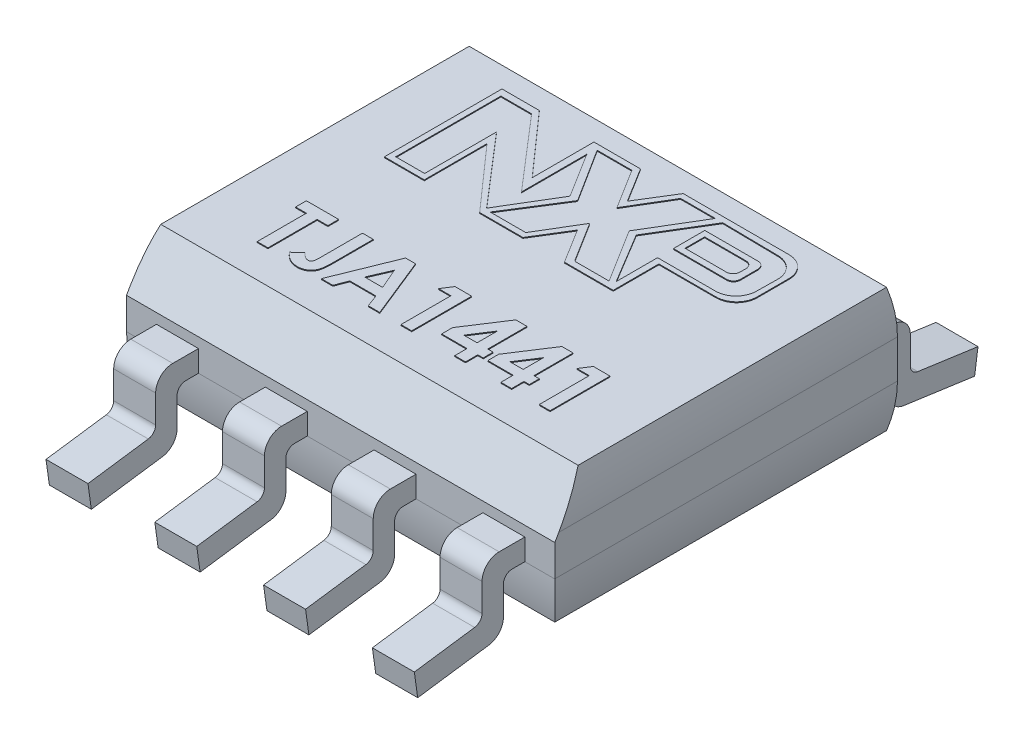
SolidWorks part; units mm, degrees
ref_plane "Front Plane" through (0, 0, 0) normal (0, 0, 1) x (1, 0, 0)
ref_plane "Top Plane" through (0, 0, 0) normal (0, 1, 0) x (1, 0, 0)
ref_plane "Right Plane" through (0, 0, 0) normal (1, 0, 0) x (0, 0, -1)
sketch "Sketch1" plane through (0, 0, 0) normal (0, 1, 0) x (1, 0, 0)
  line L1 (-2.5, 2) -> (2.5, 2)
  line L2 (-2.5, 2) -> (-2.5, -2)
  line L3 (-2.5, -2) -> (2.5, -2)
  line L4 (2.5, 2) -> (2.5, -2)
  line L5 (-2.5, 2) -> (2.5, -2) construction
  line L6 (-2.5, -2) -> (2.5, 2) construction
  point P0 (0, 0)
  dimension "D1" = 5
  dimension "D2" = 4
extrude "Boss-Extrude1" add sketch "Sketch1" along normal blind 1.45
sketch "Sketch2" plane through (-2.5, 0, 0) normal (-1, 0, 0) x (0, 0, 1)
  line L0 (2, 0.8687) -> (1.6644, 1.45)
  line L1 (2, 1.45) -> (2, 0) construction
  line L2 (-2, 1.45) -> (2, 1.45) construction
  line L3 (0, 0) -> (0, 0.828) construction
  line L4 (-2, 0.725) -> (-1.3983, 0.725) construction
  line L6 (-2, 1.45) -> (-2, 0) construction
  line L7 (-1.8644, 1.6723) -> (-2.1559, 1.6723)
  line L8 (-2.1559, 1.6723) -> (-2.1559, 0.954)
  line L9 (-2.1559, 0.954) -> (-2, 0.9484)
  line L10 (-2, 0.5016) -> (-2.1559, 0.5016)
  line L11 (-2.1559, 0.5016) -> (-2.1559, -0.2223)
  line L12 (-2.1559, -0.2223) -> (-1.8644, -0.2223)
  line L13 (1.6644, 1.45) -> (1.6644, 1.7317)
  line L14 (1.6644, 1.7317) -> (2.4871, 1.7317)
  line L15 (2.4871, 1.7317) -> (2.4871, 0.8687)
  line L16 (2.4871, 0.8687) -> (2, 0.8687)
  line L17 (2, 0.5015) -> (2.4871, 0.5015)
  line L18 (2.4871, 0.5015) -> (2.4871, -0.2223)
  line L19 (2.4871, -0.2223) -> (1.8644, -0.2223)
  arc A0 (2, 0.5015) -> (1.8644, -0.2223) centre (0, 0.5015) cw
  arc A1 (-2, 0.5016) -> (-1.8644, -0.2223) centre (0, 0.5015) ccw
  arc A2 (-2, 0.9484) -> (-1.8644, 1.6723) centre (0, 0.9485) cw
  dimension "D1" = 2
  dimension "D2" = 60
extrude "Cut-Extrude1" cut sketch "Sketch2" against normal blind 61.45
sketch "Sketch5" plane through (0, 0, -2) normal (0, 0, -1) x (-1, 0, 0)
  line L1 (0, 1.45) -> (0, 1.0867) construction
  line L2 (-3.4587, 0.725) -> (-2.857, 0.725) construction
  line L3 (-2.3644, 1.6723) -> (-2.6559, 1.6723)
  line L4 (-2.6559, 1.6723) -> (-2.6559, 0.954)
  line L5 (-2.6559, 0.954) -> (-2.5, 0.9484)
  line L6 (-2.5, 0.5016) -> (-2.6559, 0.5016)
  line L7 (-2.6559, 0.5016) -> (-2.6559, -0.2223)
  line L8 (-2.6559, -0.2223) -> (-2.3644, -0.2223)
  line L16 (2.5, 1.45) -> (-2.5, 1.45) construction
  line L17 (-2.6559, 1.6723) -> (-2.3644, 1.6723)
  line L18 (-2.6559, 0.9484) -> (-2.6559, 1.6723)
  line L19 (-2.5, 0.9484) -> (-2.6559, 0.9484)
  line L20 (-2.6559, 0.496) -> (-2.5, 0.5016)
  line L21 (-2.6559, -0.2223) -> (-2.6559, 0.496)
  line L22 (-2.3644, -0.2223) -> (-2.6559, -0.2223)
  line L23 (2.6559, -0.2223) -> (2.3644, -0.2223)
  line L24 (2.6559, 0.5016) -> (2.6559, -0.2223)
  line L25 (2.5, 0.5016) -> (2.6559, 0.5016)
  line L26 (2.6559, 0.954) -> (2.5, 0.9484)
  line L27 (2.6559, 1.6723) -> (2.6559, 0.954)
  line L28 (2.3644, 1.6723) -> (2.6559, 1.6723)
  arc A1 (-2.5, 0.5016) -> (-2.3644, -0.2223) centre (-0.5, 0.5015) ccw
  arc A2 (-2.5, 0.9484) -> (-2.3644, 1.6723) centre (-0.5, 0.9485) cw
  arc A3 (-2.5, 0.5016) -> (-2.3644, -0.2223) centre (-0.5, 0.5015) ccw
  arc A4 (-2.5, 0.9484) -> (-2.3644, 1.6723) centre (-0.5, 0.9485) cw
  arc A5 (2.5, 0.5016) -> (2.3644, -0.2223) centre (0.5, 0.5015) cw
  arc A6 (2.5, 0.9484) -> (2.3644, 1.6723) centre (0.5, 0.9485) ccw
extrude "Cut-Extrude2" cut sketch "Sketch5" against normal blind 61.45 contours L5 A2 L3 L4 | A1 L20 L7 L22 | A6 L26 L27 L28 | L25 A5 L23 L24
sketch "Sketch6" plane through (-2.5, 0, 0) normal (-1, 0, 0) x (0, 0, 1)
  line L5 (1.9361, 0) -> (-1.9361, 0) construction
  line L7 (0, 0) -> (0, -0.7239) construction
  line L8 (2.2535, 0.75) -> (2.3, 0.75)
  line L9 (2.5, 0.55) -> (2.5, 0.2276)
  line L10 (2.5, 0.1406) -> (3.25, 0.1406) construction
  line L11 (3.25, 0.1406) -> (3.25, -0.1094) construction
  line L12 (3.25, -0.1094) -> (2.25, -0.1094) construction
  line L13 (2.25, 0.0645) -> (2.25, 0.4)
  line L14 (2.25, 0.5) -> (2.2535, 0.5)
  line L15 (-3.25, -0.1094) -> (-2.25, -0.1094) construction
  line L17 (2.4222, -0.1335) -> (3.2508, -0.25)
  line L18 (2.5861, 0.1286) -> (3.2901, 0.0296)
  line L19 (3.2508, -0.25) -> (3.2901, 0.0296)
  line L20 (-3.25, 0.1406) -> (-3.25, -0.1094) construction
  line L21 (-2.5, 0.1406) -> (-3.25, 0.1406) construction
  line L22 (-3.2508, -0.25) -> (-3.2901, 0.0296)
  line L23 (-2.5861, 0.1286) -> (-3.2901, 0.0296)
  line L24 (-2.4222, -0.1335) -> (-3.2508, -0.25)
  line L25 (-2.25, 0.5) -> (-2.2535, 0.5)
  line L26 (-2.25, 0.0645) -> (-2.25, 0.4)
  line L27 (-2.5, 0.55) -> (-2.5, 0.2276)
  line L28 (-2.2535, 0.75) -> (-2.3, 0.75)
  line L29 (-2.15, 0.5) -> (2.15, 0.5)
  line L30 (-2.2535, 0.75) -> (2.2535, 0.75)
  arc A0 (2.4222, -0.1335) -> (2.25, 0.0645) centre (2.45, 0.0645) cw
  arc A1 (2.5, 0.55) -> (2.3, 0.75) centre (2.3, 0.55) ccw
  arc A2 (2.5861, 0.1286) -> (2.5, 0.2276) centre (2.6, 0.2276) cw
  arc A3 (2.25, 0.4) -> (2.15, 0.5) centre (2.15, 0.4) ccw
  arc A4 (-2.25, 0.4) -> (-2.15, 0.5) centre (-2.15, 0.4) cw
  arc A5 (-2.5861, 0.1286) -> (-2.5, 0.2276) centre (-2.6, 0.2276) ccw
  arc A6 (-2.5, 0.55) -> (-2.3, 0.75) centre (-2.3, 0.55) cw
  arc A7 (-2.4222, -0.1335) -> (-2.25, 0.0645) centre (-2.45, 0.0645) ccw
  dimension "D9" = 0.2
  dimension "D10" = 0.1
  dimension "D4" = 0.25
  dimension "D5" = 0.25
  dimension "D6" = 1
  dimension "D7" = 8
  dimension "D8" = 0.25
extrude "Boss-Extrude2" add sketch "Sketch6" against normal up to surface (5 mm away) up to face at (2.5, 0.8431, 0.3908)
sketch "Sketch7" plane through (0, 1.45, 0) normal (0, 1, 0) x (1, 0, 0)
  line L0 (2.5, -2) -> (-2.5, -2) construction
  line L1 (-2.5, -2) -> (-2.15, -2)
  line L2 (-2.5, -2) -> (-2.5, -3.534)
  line L3 (-2.5, -3.534) -> (-2.15, -3.534)
  line L4 (-2.15, -2) -> (-2.15, -3.534)
  line L5 (-1.66, -2) -> (-0.88, -2)
  line L6 (-1.66, -2) -> (-1.66, -3.6106)
  line L7 (-1.66, -3.6106) -> (-0.88, -3.6106)
  line L8 (-0.88, -2) -> (-0.88, -3.6106)
  line L9 (0, 0) -> (-3.4858, 0) construction
  line L10 (-0.39, -2) -> (0.39, -2)
  line L11 (-0.39, -2) -> (-0.39, -3.6106)
  line L12 (-0.39, -3.6106) -> (0.39, -3.6106)
  line L13 (0.39, -2) -> (0.39, -3.6106)
  line L14 (2.5, -2) -> (2.15, -2)
  line L15 (2.5, -2) -> (2.5, -3.783)
  line L16 (2.5, -3.783) -> (2.15, -3.783)
  line L17 (2.15, -2) -> (2.15, -3.783)
  line L18 (1.66, -2) -> (0.88, -2)
  line L19 (1.66, -2) -> (1.66, -3.6776)
  line L20 (1.66, -3.6776) -> (0.88, -3.6776)
  line L21 (0.88, -2) -> (0.88, -3.6776)
  line L22 (0.88, 2) -> (0.88, 3.6776)
  line L23 (1.66, 3.6776) -> (0.88, 3.6776)
  line L24 (1.66, 2) -> (1.66, 3.6776)
  line L25 (1.66, 2) -> (0.88, 2)
  line L26 (2.15, 2) -> (2.15, 3.783)
  line L27 (2.5, 3.783) -> (2.15, 3.783)
  line L28 (2.5, 2) -> (2.5, 3.783)
  line L29 (2.5, 2) -> (2.15, 2)
  line L30 (0.39, 2) -> (0.39, 3.6106)
  line L31 (-0.39, 3.6106) -> (0.39, 3.6106)
  line L32 (-0.39, 2) -> (-0.39, 3.6106)
  line L33 (-0.39, 2) -> (0.39, 2)
  line L34 (-0.88, 2) -> (-0.88, 3.6106)
  line L35 (-1.66, 3.6106) -> (-0.88, 3.6106)
  line L36 (-1.66, 2) -> (-1.66, 3.6106)
  line L37 (-1.66, 2) -> (-0.88, 2)
  line L38 (-2.15, 2) -> (-2.15, 3.534)
  line L39 (-2.5, 3.534) -> (-2.15, 3.534)
  line L40 (-2.5, 2) -> (-2.5, 3.534)
  line L41 (-2.5, 2) -> (-2.15, 2)
  dimension "D1" = 0.49
  dimension "D2" = 0.49
  dimension "D3" = 0.49
  dimension "D4" = 0.49
  dimension "D5" = 0.78
  dimension "D6" = 0.78
  dimension "D7" = 0.78
  dimension "D8" = 0.35
extrude "Cut-Extrude3" cut sketch "Sketch7" against normal blind 61.45
sketch "Sketch8" plane through (0, 1.45, 0) normal (0, 1, 0) x (1, 0, 0)
  line L0 (70.6653, 255.7964) -> (518.6653, 255.7964) construction
  line L1 (-1.8034, 0.3139) -> (-1.8034, 1.6861)
  line L2 (-1.8034, 1.6861) -> (-1.3672, 1.6861)
  line L3 (-1.3672, 1.6861) -> (-0.7295, 0.965)
  line L4 (-0.7295, 0.965) -> (-0.7295, 1.6861)
  line L5 (-0.7295, 1.6861) -> (-0.186, 1.6861)
  line L6 (-0.186, 1.6861) -> (0.0636, 1.2836)
  line L7 (0.0636, 1.2836) -> (0.3123, 1.6861)
  line L8 (0.3123, 1.6861) -> (1.5487, 1.6861)
  line L9 (1.7887, 1.4461) -> (1.7887, 1.0732)
  line L10 (1.5487, 0.8332) -> (0.8817, 0.8332)
  line L11 (0.8817, 0.8332) -> (0.8817, 0.2999)
  line L12 (0.8817, 0.2999) -> (0.3123, 0.2999)
  line L13 (0.3123, 0.2999) -> (0.0636, 0.7007)
  line L14 (0.0636, 0.7007) -> (-0.1796, 0.3069)
  line L15 (-0.1796, 0.3069) -> (-0.6842, 0.3069)
  line L16 (-0.6842, 0.3069) -> (-1.3377, 1.046)
  line L17 (-1.3377, 1.046) -> (-1.3377, 0.3139)
  line L18 (-1.3377, 0.3139) -> (-1.8034, 0.3139)
  line L19 (-1.7377, 0.3801) -> (-1.7377, 1.6079)
  line L20 (-1.7377, 1.6079) -> (-1.3789, 1.6079)
  line L21 (-1.3789, 1.6079) -> (-0.6481, 0.759)
  line L22 (-0.6481, 0.759) -> (-0.6481, 1.5221)
  line L23 (-0.6481, 1.5221) -> (-0.3221, 0.9996)
  line L24 (-0.3221, 0.9996) -> (-0.6875, 0.3914)
  line L25 (-0.6875, 0.3914) -> (-1.3999, 1.219)
  line L26 (-1.3999, 1.219) -> (-1.3999, 0.3801)
  line L27 (-1.3999, 0.3801) -> (-1.7377, 0.3801)
  line L28 (-0.6279, 1.6222) -> (-0.2222, 1.6222)
  line L29 (-0.2222, 1.6222) -> (0.068, 1.1578)
  line L30 (0.068, 1.1578) -> (0.3464, 1.6222)
  line L31 (0.3464, 1.6222) -> (0.7514, 1.6222)
  line L32 (0.7514, 1.6222) -> (0.3743, 0.9932)
  line L33 (0.3743, 0.9932) -> (0.7643, 0.369)
  line L34 (0.7643, 0.369) -> (0.3619, 0.369)
  line L35 (0.3619, 0.369) -> (0.068, 0.8394)
  line L36 (0.068, 0.8394) -> (-0.2117, 0.373)
  line L37 (-0.2117, 0.373) -> (-0.6279, 0.373)
  line L38 (-0.6279, 0.373) -> (-0.2334, 0.9996)
  line L39 (-0.2334, 0.9996) -> (-0.6279, 1.6222)
  line L40 (0.8381, 1.6222) -> (1.4939, 1.613)
  line L41 (1.7305, 1.3696) -> (1.727, 1.1248)
  line L42 (1.4871, 0.8882) -> (0.8112, 0.8882)
  line L43 (0.8112, 0.8882) -> (0.8112, 0.4059)
  line L44 (0.8112, 0.4059) -> (0.4571, 0.9932)
  line L45 (0.4571, 0.9932) -> (0.8381, 1.6222)
  line L46 (0.8112, 1.4396) -> (1.433, 1.4396)
  line L47 (1.513, 1.3596) -> (1.513, 1.1532)
  line L48 (1.433, 1.0732) -> (0.8112, 1.0732)
  line L49 (0.8112, 1.4396) -> (0.8112, 1.0732)
  line L50 (0.8755, 1.3732) -> (1.3583, 1.3732)
  line L51 (0.8755, 1.3732) -> (0.8755, 1.144)
  line L52 (0.8755, 1.144) -> (1.3583, 1.144)
  line L53 (1.4383, 1.2932) -> (1.4383, 1.224)
  arc A0 (1.7887, 1.0732) -> (1.5487, 0.8332) centre (1.5487, 1.0732) cw
  arc A1 (1.5487, 1.6861) -> (1.7887, 1.4461) centre (1.5487, 1.4461) cw
  arc A2 (1.727, 1.1248) -> (1.4871, 0.8882) centre (1.4871, 1.1282) cw
  arc A3 (1.4939, 1.613) -> (1.7305, 1.3696) centre (1.4905, 1.373) cw
  arc A4 (1.3583, 1.144) -> (1.4383, 1.224) centre (1.3583, 1.224) ccw
  arc A5 (1.3583, 1.3732) -> (1.4383, 1.2932) centre (1.3583, 1.2932) cw
  arc A6 (1.513, 1.1532) -> (1.433, 1.0732) centre (1.433, 1.1532) cw
  arc A7 (1.433, 1.4396) -> (1.513, 1.3596) centre (1.433, 1.3596) cw
  point P74 (-1.6757, -1.4042)
  point P75 (-1.8034, -1.455)
  point P76 (-1.8563, -1.4155)
  point P77 (-1.8034, -1.4268)
extrude "Boss-Extrude3" add sketch "Sketch8" along normal blind 0.01 contours A1 L8 L7 L6 L5 L4 L3 L2 L1 L18 L17 L16 L15 L14 L13 L12 L11 L10 A0 L9 L38 L39 L28 L29 L30 L31 L32 L33 L34 L35 L36 L37 L26 L27 L19 L20 L21 L22 L23 L24 L25 L40 A3 L41 A2 L42 L43 L44 | A7 L46 L49 L48 A6 L47 L50 A5 L53 A4 L52 L51
sketch "Sketch9" plane through (0, 1.45, 0) normal (0, 1, 0) x (1, 0, 0)
  line L0 (-1.8233, -1.2861) -> (2.2013, -1.2861) construction
  text T0 "<b>TJA1441</b>" font "Century Gothic" height 0.7
  point P3 (-1.8959, -1.1475)
  point P4 (-1.8233, -1.2861)
extrude "Boss-Extrude4" add sketch "Sketch9" along normal blind 0.01
